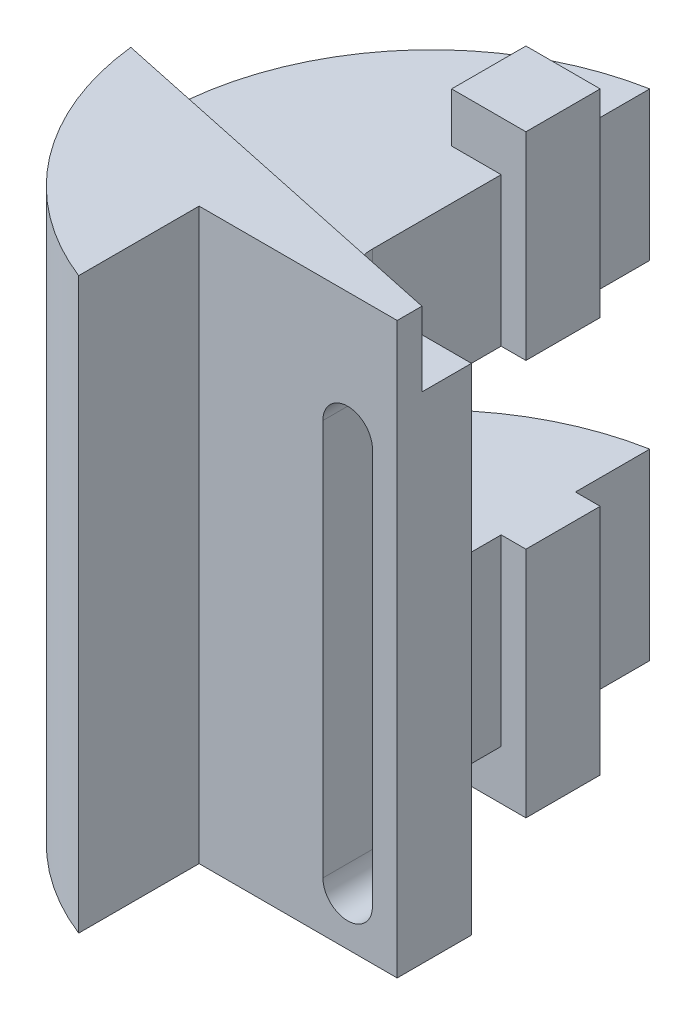
SolidWorks part; units mm, degrees
material "1060 Alloy"
ref_plane "Front Plane" through (0, 0, 0) normal (0, 0, 1) x (1, 0, 0)
ref_plane "Top Plane" through (0, 0, 0) normal (0, 1, 0) x (1, 0, 0)
ref_plane "Right Plane" through (0, 0, 0) normal (1, 0, 0) x (0, 0, -1)
sketch "Sketch1" plane through (0, 0, 0) normal (0, 1, 0) x (1, 0, 0)
  line L0 (0, 83.803) -> (0, -84.3516) construction
  line L1 (-131.1222, 0) -> (151.1471, 0) construction
  line L2 (0, 15) -> (0, 0)
  line L3 (0, 0) -> (-40, 0)
  line L4 (-40, 0) -> (-40, -24.318)
  line L5 (-30, 81) -> (-30, 25)
  line L6 (-20, 15) -> (0, 15)
  line L8 (-40, 66) -> (-25, 66)
  line L9 (-40, 66) -> (-40, 51)
  line L10 (-40, 51) -> (-25, 51)
  line L11 (-25, 66) -> (-25, 51)
  arc A0 (-40, -24.318) -> (-30, 81) centre (-20, 26.9167) cw
  arc A1 (27.9634, 0) -> (16.998, -13.7791) centre (-20, 26.9167) cw
  arc A2 (-30, 25) -> (-20, 15) centre (-20, 25) ccw
  point P14 (-30, 81)
  point P21 (0, 0)
  dimension "D1" = 55
  dimension "D6" = 10
  dimension "D7" = 66
  dimension "D2" = 40
  dimension "D3" = 15
  dimension "D4" = 20
  dimension "D5" = 10
  dimension "D8" = 5
  dimension "D9" = 15
  dimension "D10" = 15
  dimension "D11" = 15
extrude "Boss-Extrude4" add sketch "Sketch1" along normal mid plane 100 contours A2 L5 L10 L9 L8 A0 L4 L3 L2 L6 region at (-46.1462, 0, -26.017)
extrude "Boss-Extrude5" add sketch "Sketch1<7>" along normal mid plane 120 contours L11 L8 L5 L10 | L9 L10 L5 L8 region at (-35, 0, -58.5) region at (-27.5, 0, -58.5)
sketch "Sketch1<7>" plane through (0, 0, 0) normal (0, 1, 0) x (1, 0, 0) same geometry as "Sketch1"
sketch "Sketch5" plane through (0, 0, 0) normal (1, 0, 0) x (0, 0, -1)
  line L1 (41, 20) -> (81, 20)
  line L2 (41, 20) -> (41, -13)
  line L3 (41, -13) -> (81, -13)
  line L4 (81, 20) -> (81, -13)
  line L5 (81, 50) -> (81, -50) construction
  dimension "D1" = 30
  dimension "D2" = 33
  dimension "D3" = 40
  dimension "D4" = 0
extrude "Cut-Extrude1" cut sketch "Sketch5" against normal blind 120
sketch "Sketch6" plane through (0, 50, 0) normal (0, 1, 0) x (1, 0, 0)
  line L0 (0, 5) -> (-74.6667, 20.8709)
  line L1 (0, 15) -> (0, 0) construction
  line L2 (0, 200083.803) -> (0, -200084.3516) construction
  line L3 (0, 5) -> (0, 0)
  line L4 (0, 0) -> (-40, 0)
  line L5 (-40, 0) -> (-40, -24.318)
  arc A0 (-30, 81) -> (-40, -24.318) centre (-20, 26.9167) ccw construction
  arc A1 (-74.6667, 20.8709) -> (-40, -24.318) centre (-20, 26.9167) ccw
  dimension "D1" = 5
  dimension "D2" = 78
extrude "Boss-Extrude6" add sketch "Sketch6" along normal blind 15
sketch "Sketch8" plane through (0, 0, -15) normal (0, 0, -1) x (-1, 0, 0)
  line L0 (10, 40) -> (10, -40) construction
  line L1 (15, 40) -> (15, -40)
  line L2 (5, 40) -> (5, -40)
  line L3 (40, 50) -> (30, 50) construction
  arc A0 (15, 40) -> (5, 40) centre (10, 40) ccw
  arc A1 (5, -40) -> (15, -40) centre (10, -40) ccw
  point P2 (10, 0)
  dimension "D1" = 10
  dimension "D2" = 80
  dimension "D3" = 10
  dimension "D4" = 10
extrude "Cut-Extrude3" cut sketch "Sketch8" against normal blind 67
